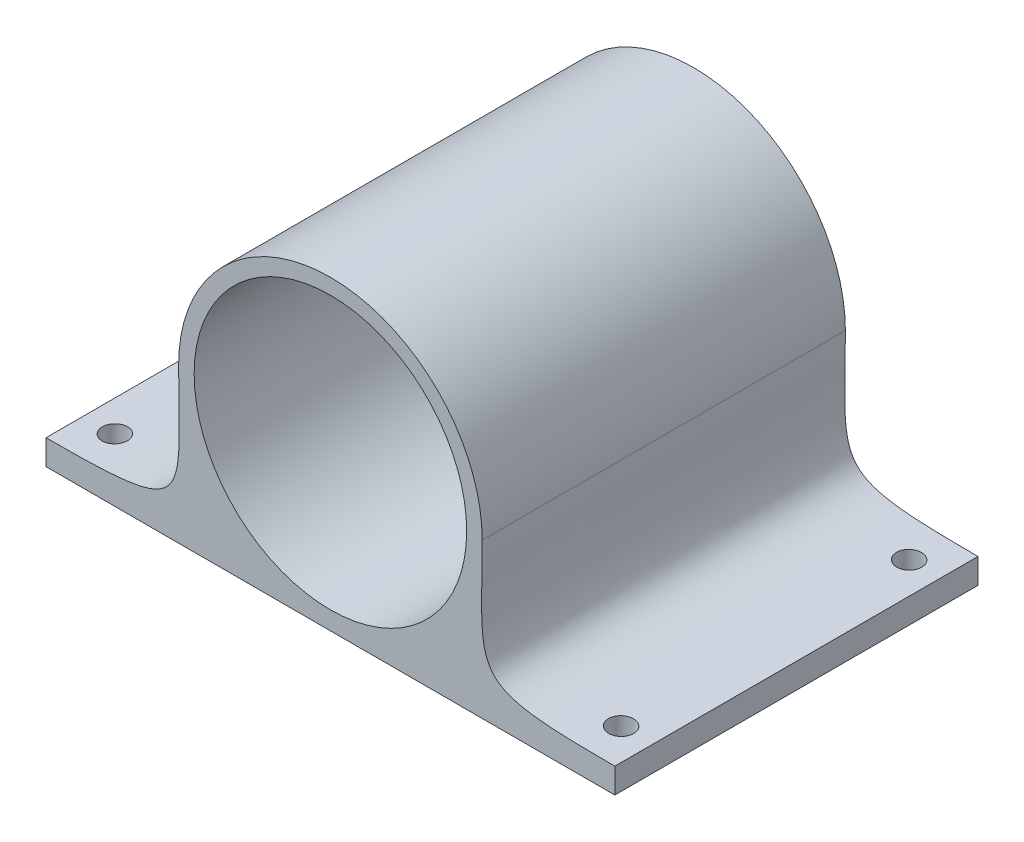
SolidWorks part; units mm, degrees
ref_plane "Front Plane" through (0, 0, 0) normal (0, 0, 1) x (1, 0, 0)
ref_plane "Top Plane" through (0, 0, 0) normal (0, 1, 0) x (1, 0, 0)
ref_plane "Right Plane" through (0, 0, 0) normal (1, 0, 0) x (0, 0, -1)
sketch "Sketch1" plane through (0, 0, 0) normal (0, 0, 1) x (1, 0, 0)
  line L0 (-45.4219, -24.6662) -> (45.4219, -24.6662)
  line L1 (-45.4219, -20.6662) -> (-45.4219, -24.6662)
  line L2 (0, 0) -> (0, -11.8779)
  line L3 (45.4219, -20.6662) -> (45.4219, -24.6662)
  circle A0 centre (0, 0) radius 21.76
  circle A1 centre (0, 0) radius 24.2415
  circle A2 centre (0, 0) radius 10
  spline S0 degree 3 poles (-45.4219, -20.6662) (-21.5322, -20.6662) (-24.2415, -19.0788) (-24.2415, 0) knots 0 0 0 0 1 1 1 1
  spline S2 degree 3 poles (45.4219, -20.6662) (21.5322, -20.6662) (24.2415, -19.0788) (24.2415, 0) knots 0 0 0 0 1 1 1 1
  point P11 (0, -24.6662)
extrude "Boss-Extrude1" add sketch "Sketch1" along normal blind 58 contours A1 A0 | L3 S2 A1 S0 L1 L0 region at (-44.4806, -22.6662, 0) region at (0, 23.5558, 0)
extrude "Boss-Extrude2" add sketch "Sketch1<4>" along normal blind 3 contours A0 region at (-21.1445, 0, 0)
sketch "Sketch1<4>" plane through (0, 0, 0) normal (0, 0, 1) x (1, 0, 0) same geometry as "Sketch1"
sketch "Sketch2" plane through (0, 0, 0) normal (0, 1, 0) x (1, 0, 0)
  line L0 (-24.1489, 0) -> (-45.4219, 0) construction
  line L1 (-45.4219, -58) -> (-45.4219, 0) construction
  line L2 (0, -0.3758) -> (0, -52.5937)
  line L3 (-45.4219, -58) -> (-24.1489, -58) construction
  circle A0 centre (-40.4219, -6) radius 2
  circle A7 centre (40.4219, -6) radius 2
  circle A8 centre (-40.4219, -52) radius 2.006
  circle A10 centre (40.4219, -52) radius 2.006
  point P14 (0, -29.0869)
  dimension "D1" = 6
  dimension "D2" = 5
  dimension "D3" = 5
  dimension "D4" = 6
extrude "Cut-Extrude2" cut sketch "Sketch2" against normal blind 30 contours A0 | A7 region at (-40.4219, 0, 6) region at (40.4219, 0, 6)
extrude "Cut-Extrude3" cut sketch "Sketch2<3>" against normal blind 30 contours A8 | A10 region at (-40.4219, 0, 52) region at (40.4219, 0, 52)
sketch "Sketch2<3>" plane through (0, 0, 0) normal (0, 1, 0) x (1, 0, 0) same geometry as "Sketch2"
